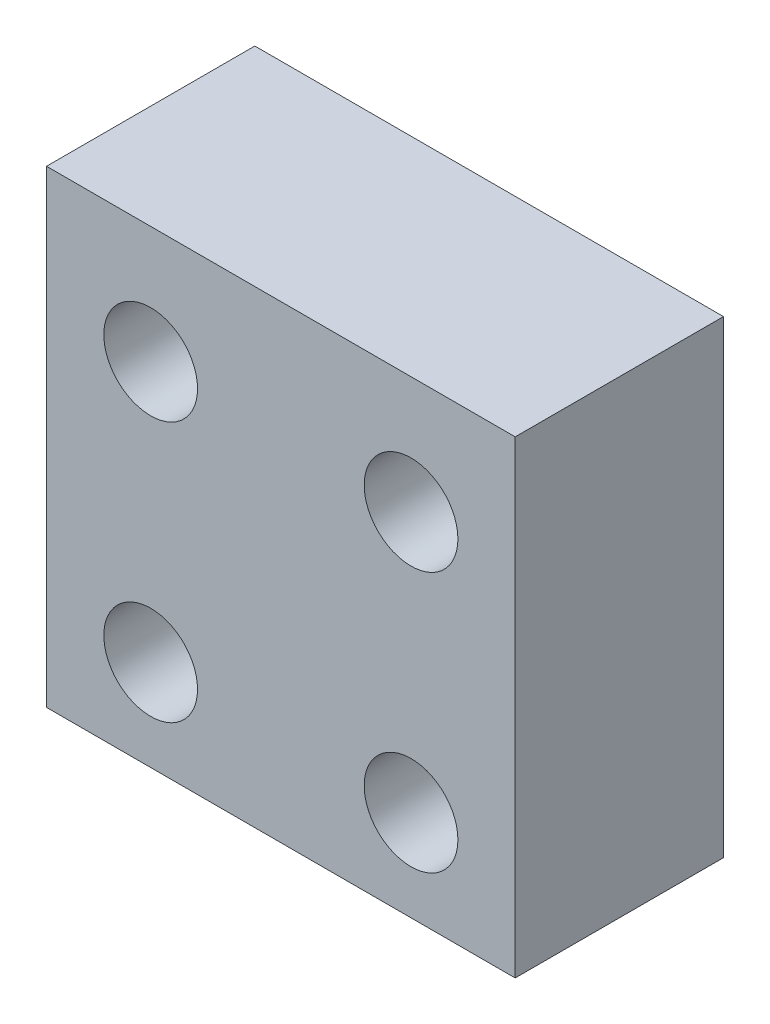
SolidWorks part; units mm, degrees
ref_plane "Front Plane" through (0, 0, 0) normal (0, 0, 1) x (1, 0, 0)
ref_plane "Top Plane" through (0, 0, 0) normal (0, 1, 0) x (1, 0, 0)
ref_plane "Right Plane" through (0, 0, 0) normal (1, 0, 0) x (0, 0, -1)
sketch "Sketch1" plane through (0, 0, 0) normal (0, 0, 1) x (1, 0, 0)
  line L0 (169, 104.999) -> (151, 104.999)
  line L8 (169, 86.999) -> (169, 104.999)
  line L10 (151, 104.999) -> (151, 86.999)
  line L11 (151, 86.999) -> (169, 86.999)
  point P6 (151, 103.9762)
  dimension "D2" = 18
extrude "Boss-Extrude1" add sketch "Sketch1" along normal blind 8
sketch "Sketch2" plane through (0, 0, 8) normal (0, 0, 1) x (1, 0, 0)
  point P0 (165, 90.499)
  point P3 (155, 90.499)
  point P6 (155, 100.499)
  point P9 (165, 100.499)
hole_wizard "M3 Clearance Hole1" positions "Sketch2" profile "Sketch3" hole size "M3" standard "ANSI Metric" end condition through all
sketch "Sketch3" plane through (165, 90.499, 8) normal (1, 0, 0) x (0, -1, 0)
  line L0 (0, 0) -> (0, 8)
  line L1 (0, 8) -> (1.8, 8)
  line L2 (1.8, 8) -> (1.8, 0)
  line L5 (1.8, 0) -> (0, 0)
  line L11 (0, -6.35) -> (0, 107.95) construction
  dimension "Thru Hole Dia." = 3.6
  dimension "Thru Hole Depth" = 8
